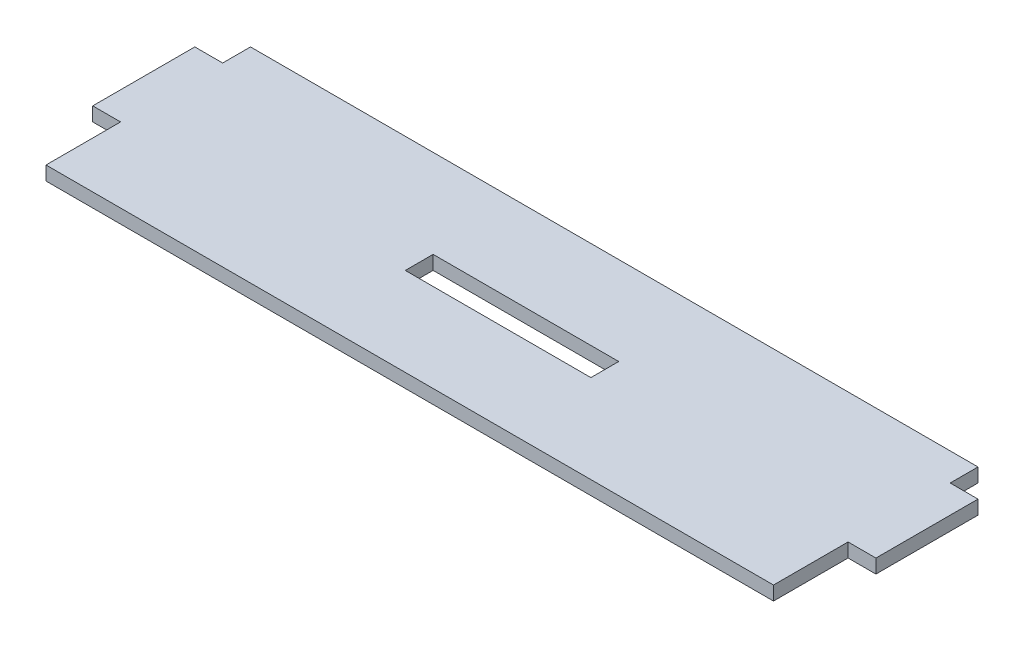
SolidWorks part; units mm, degrees
ref_plane "Front Plane" through (0, 0, 0) normal (0, 0, 1) x (1, 0, 0)
ref_plane "Top Plane" through (0, 0, 0) normal (0, 1, 0) x (1, 0, 0)
ref_plane "Right Plane" through (0, 0, 0) normal (1, 0, 0) x (0, 0, -1)
sketch "Sketch2" plane through (0, 0, 0) normal (0, 1, 0) x (1, 0, 0)
  line L0 (0, -6) -> (-6, -6)
  line L1 (0, 0) -> (156.78, 0)
  line L2 (0, 0) -> (0, -6)
  line L3 (0, -44.07) -> (156.78, -44.07)
  line L4 (156.78, 0) -> (156.78, -6)
  line L5 (-6, -6) -> (-6, -28)
  line L6 (-6, -28) -> (0, -28)
  line L7 (78.39, 0) -> (78.39, -36.6386) construction
  line L8 (162.78, -28) -> (156.78, -28)
  line L9 (162.78, -6) -> (162.78, -28)
  line L10 (156.78, -6) -> (162.78, -6)
  line L11 (0, -28) -> (0, -44.07)
  line L12 (156.78, -28) -> (156.78, -44.07)
  line L13 (8.7933, 0) -> (8.7933, -44.07) construction
  line L14 (8.7933, -22.035) -> (150.2461, -22.035) construction
  line L15 (58.39, -19.035) -> (58.39, -25.035)
  line L16 (58.39, -25.035) -> (98.39, -25.035)
  line L17 (98.39, -19.035) -> (98.39, -25.035)
  line L18 (58.39, -19.035) -> (98.39, -19.035)
  point P24 (78.39, -25.035)
  point P25 (98.39, -22.035)
  point P26 (58.39, -22.035)
  dimension "D1" = 168.78
  dimension "D2" = 44.07
  dimension "D3" = 6
  dimension "D4" = 22
  dimension "D5" = 6
  dimension "D6" = 20
  dimension "D7" = 3
extrude "Boss-Extrude1" add sketch "Sketch2" along normal blind 3
